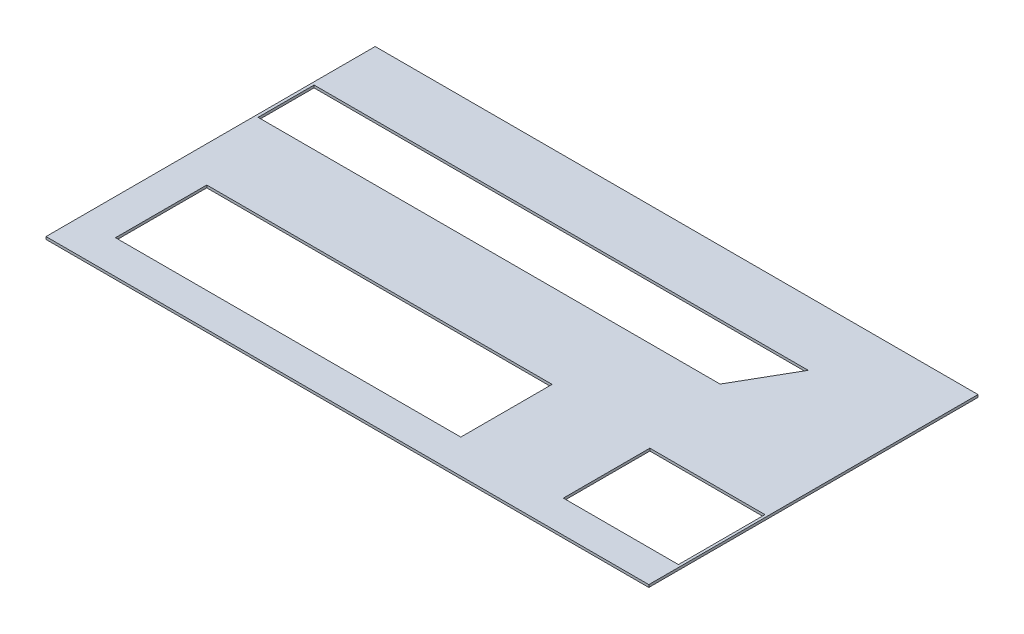
SolidWorks part; units mm, degrees
material "Particle Board"
ref_plane "Front Plane" through (0, 0, 0) normal (0, 0, 1) x (1, 0, 0)
ref_plane "Top Plane" through (0, 0, 0) normal (0, 1, 0) x (1, 0, 0)
ref_plane "Right Plane" through (0, 0, 0) normal (1, 0, 0) x (0, 0, -1)
sketch "Sketch1" plane through (0, 0, 0) normal (0, 1, 0) x (1, 0, 0)
  line L1 (0, 0) -> (1518.68, 0)
  line L2 (0, 0) -> (0, 829.31)
  line L3 (0, 829.31) -> (1518.68, 829.31)
  line L4 (1518.68, 0) -> (1518.68, 829.31)
  dimension "D1" = 1518.68
  dimension "D2" = 829.31
extrude "Boss-Extrude1" add sketch "Sketch1" along normal blind 6.35
sketch "Sketch2" plane through (0, 6.35, 0) normal (0, 1, 0) x (1, 0, 0)
  line L0 (0, 829.31) -> (0, 0) construction
  line L1 (90, 85) -> (960, 85)
  line L2 (90, 85) -> (90, 315)
  line L3 (90, 315) -> (960, 315)
  line L4 (960, 85) -> (960, 315)
  line L5 (0, 0) -> (1518.68, 0) construction
  line L6 (1518.68, 0) -> (1518.68, 829.31) construction
  line L7 (7, 668.31) -> (1252, 668.31)
  line L8 (7, 668.31) -> (7, 527.31)
  line L9 (7, 527.31) -> (1171, 527.31)
  line L11 (1512.33, 299) -> (1222.33, 299)
  line L12 (1512.33, 299) -> (1512.33, 81)
  line L13 (1512.33, 81) -> (1222.33, 81)
  line L14 (1222.33, 299) -> (1222.33, 81)
  line L15 (1252, 668.31) -> (1171, 527.31)
  line L16 (1518.68, 829.31) -> (0, 829.31) construction
  dimension "D1" = 870
  dimension "D2" = 230
  dimension "D3" = 90
  dimension "D4" = 85
  dimension "D5" = 81
  dimension "D6" = 218
  dimension "D7" = 6.35
  dimension "D8" = 290
  dimension "D9" = 7
  dimension "D10" = 1245
  dimension "D11" = 1164
  dimension "D12" = 161
  dimension "D13" = 141
extrude "Cut-Extrude1" cut sketch "Sketch2" against normal up to next
